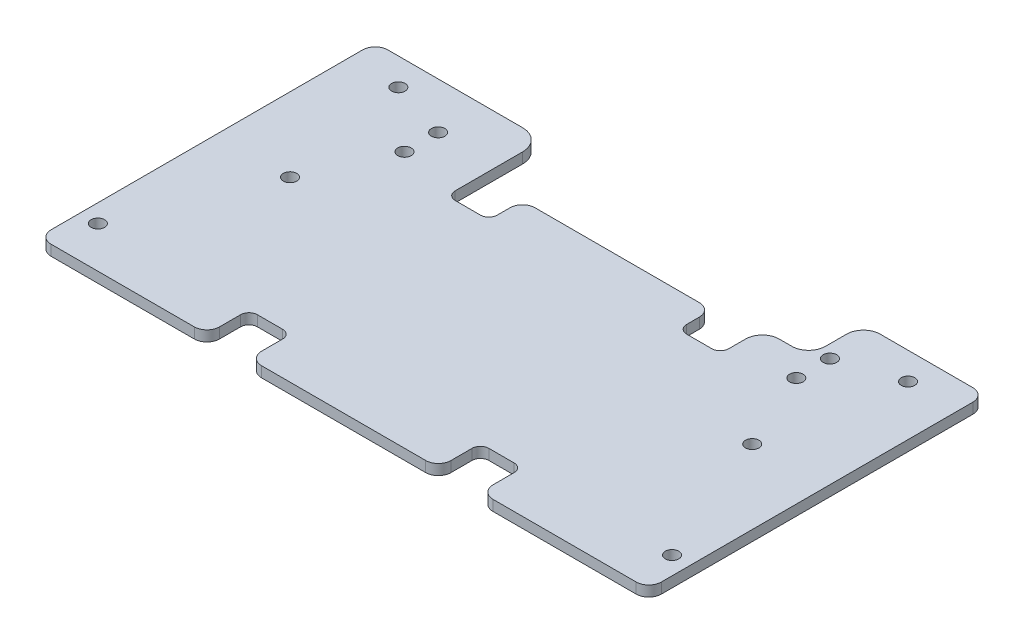
SolidWorks part; units mm, degrees
ref_plane "Front Plane" through (0, 0, 0) normal (0, 0, 1) x (1, 0, 0)
ref_plane "Top Plane" through (0, 0, 0) normal (0, 1, 0) x (1, 0, 0)
ref_plane "Right Plane" through (0, 0, 0) normal (1, 0, 0) x (0, 0, -1)
sketch "Sketch1" plane through (0, 0, 0) normal (0, 1, 0) x (1, 0, 0)
  line L0 (0, 0) -> (0, -101.6)
  line L1 (0, -101.6) -> (184.15, -101.6)
  line L2 (184.15, -101.6) -> (184.15, 0)
  line L4 (50.8, 0) -> (50.8, -19.05)
  line L5 (50.8, -19.05) -> (133.35, -19.05)
  line L6 (133.35, -19.05) -> (133.35, 0)
  line L7 (0, 0) -> (50.8, 0)
  line L8 (133.35, 0) -> (184.15, 0)
  line L9 (50.8, -19.05) -> (50.8, -29.21)
  line L10 (50.8, -29.21) -> (63.5, -29.21)
  line L11 (63.5, -29.21) -> (63.5, -19.05)
  line L12 (133.35, -19.05) -> (133.35, -29.21)
  line L13 (133.35, -29.21) -> (120.65, -29.21)
  line L14 (120.65, -29.21) -> (120.65, -19.05)
  line L15 (50.8, -101.6) -> (50.8, -88.9)
  line L16 (50.8, -88.9) -> (63.5, -88.9)
  line L17 (63.5, -88.9) -> (63.5, -101.6)
  line L18 (120.65, -101.6) -> (120.65, -88.9)
  line L19 (120.65, -88.9) -> (133.35, -88.9)
  line L20 (133.35, -88.9) -> (133.35, -101.6)
  line L21 (92.075, -101.6) -> (92.075, -19.05) construction
  dimension "D1" = 184.15
  dimension "D2" = 82.55
  dimension "D3" = 12.7
  dimension "D4" = 10.16
  dimension "D5" = 19.05
  dimension "D6" = 101.6
  dimension "D7" = 12.7
extrude "Boss-Extrude1" add sketch "Sketch1" along normal blind 3.175 contours L2 L0 L1 | L21 L1 L18 L19 L20 L2 L8 L6 L12 L13 L14 L5 region at (43.2352, 0, 54.2701) region at (140.9148, 0, 54.2701)
fillet "Fillet1" radius 3.81 4 edges at (184.15, 1.5875, 101.6) (0, 1.5875, 101.6) (184.15, 1.5875, 0) (0, 1.5875, 0)
sketch "Sketch2" plane through (0, 3.175, 0) normal (0, 1, 0) x (1, 0, 0)
  line L0 (92.075, -101.6) -> (92.075, -19.05) construction
  line L1 (63.5, -101.6) -> (120.65, -101.6) construction
  line L2 (63.5, -19.05) -> (120.65, -19.05) construction
  circle A4 centre (5.4374, -89.1463) radius 2.032 construction
  circle A5 centre (5.4374, -89.1463) radius 2.032
  circle A6 centre (22.3389, -48.035) radius 2.032 construction
  circle A7 centre (178.7126, -89.1463) radius 2.032
  circle A8 centre (15.1663, -8.1952) radius 2.032 construction
  circle A9 centre (22.3389, -48.035) radius 2.032
  circle A11 centre (15.1663, -8.1952) radius 2.032
  circle A24 centre (32.9463, -24.13) radius 2.032 construction
  circle A25 centre (32.9463, -13.97) radius 2.032 construction
  circle A26 centre (32.9463, -24.13) radius 2.032
  circle A27 centre (32.9463, -13.97) radius 2.032
  circle A34 centre (32.9463, -13.97) radius 2.032
  circle A35 centre (32.9463, -24.13) radius 2.032
  circle A37 centre (161.8111, -48.035) radius 2.032
  circle A38 centre (151.2037, -24.13) radius 2.032
  circle A39 centre (151.2037, -13.97) radius 2.032
  circle A40 centre (168.9837, -8.1952) radius 2.032
extrude "Cut-Extrude1" cut sketch "Sketch2" against normal through all contours A11 | A9 | A5 | A26 | A27 | A37 | A38 | A7 | A39 | A40 region at (5.4374, 3.175, 89.1463) region at (22.3389, 3.175, 48.035) region at (15.1663, 3.175, 8.1952) region at (32.9463, 3.175, 24.13) region at (32.9463, 3.175, 13.97)
fillet "Fillet2" radius 6.35 2 edges at (50.8, 1.5875, 0) (133.35, 1.5875, 0)
fillet "Fillet3" radius 2.54 8 edges at (133.35, 1.5875, 29.21) (120.65, 1.5875, 29.21) (50.8, 1.5875, 29.21) (63.5, 1.5875, 29.21) (133.35, 1.5875, 88.9) (120.65, 1.5875, 88.9) (63.5, 1.5875, 88.9) (50.8, 1.5875, 88.9)
fillet "Fillet4" radius 3.81 2 edges at (120.65, 1.5875, 19.05) (63.5, 1.5875, 19.05)
fillet "Fillet5" radius 3.81 4 edges at (133.35, 1.5875, 101.6) (120.65, 1.5875, 101.6) (63.5, 1.5875, 101.6) (50.8, 1.5875, 101.6)
ref_plane "Plane1" through (0, 2.8036, -1.0204) normal (0, 0.9397, -0.342) x (1, 0, 0)
sketch "Sketch9" plane through (0, 0, 0) normal (0, -1, 0) x (1, 0, 0)
  line L0 (133.35, 16.51) -> (147.32, 16.51)
  line L1 (133.35, 26.67) -> (133.35, 6.35) construction
  line L2 (147.32, 16.51) -> (147.32, 0)
  line L3 (139.7, 0) -> (180.34, 0) construction
  point P4 (144.4376, 0)
  line M42 (133.35, 26.67) -> (133.35, 6.35)
  arc M43 (133.35, 6.35) -> (139.7, 0) centre (139.7, 6.35) ccw
  line M44 (139.7, 0) -> (180.34, 0)
  dimension "D1" = 13.97
  dimension "D2" = 16.51
extrude "Cut-Extrude2" cut sketch "Sketch9" against normal through all and the other way through all contours L2 L0 M42 M43 M44 region at (140.552, 0, 8.5215)
fillet "Fillet6" radius 5.08 3 edges at (147.32, 1.5875, 0) (147.32, 1.5875, 16.51) (133.35, 1.5875, 16.51)
